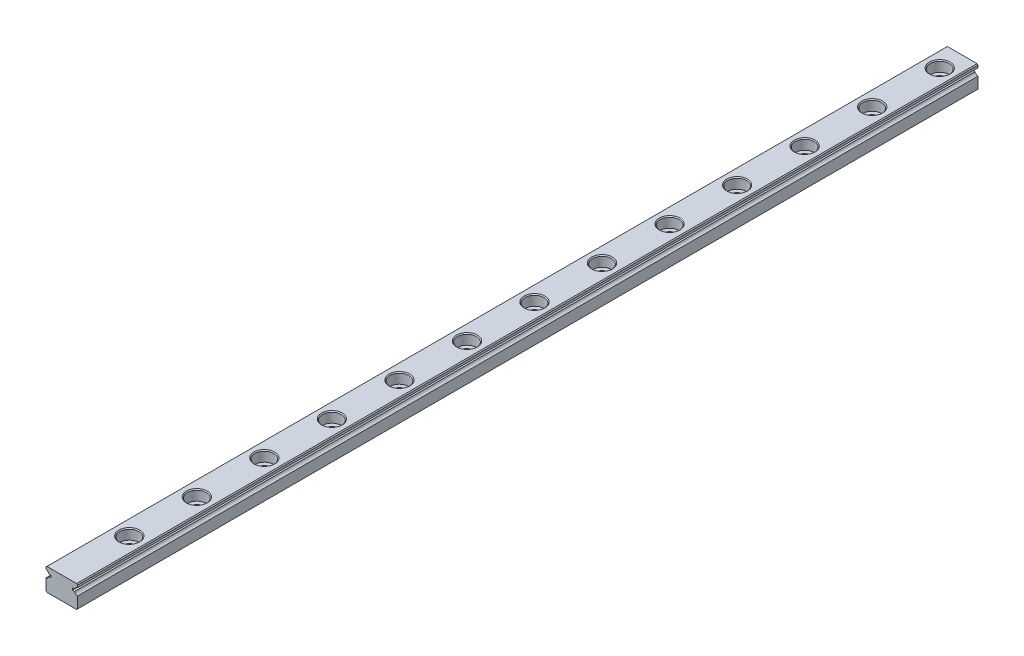
SolidWorks part; units mm, degrees
ref_plane "Спереди" through (0, 0, 0) normal (0, 0, 1) x (1, 0, 0)
ref_plane "Сверху" through (0, 0, 0) normal (0, 1, 0) x (1, 0, 0)
ref_plane "Справа" through (0, 0, 0) normal (1, 0, 0) x (0, 0, -1)
sketch "Sketch1" plane through (0, 0, 0) normal (0, 0, 1) x (1, 0, 0)
  line L0 (0, 0) -> (0, 4.3706) construction
  line L1 (-3.3, -2.5) -> (3.3, -2.5)
  line L2 (-3.5, -2.3) -> (-3.5, 0.2063)
  line L3 (-3.3, 2.5) -> (3.3, 2.5)
  line L4 (3.5, -2.3) -> (3.5, 0.2063)
  line L5 (-3.5, -2.5) -> (3.5, 2.5) construction
  line L6 (-3.5, 2.5) -> (3.5, -2.5) construction
  line L7 (-3.5, 1.7937) -> (-3.5, 2.3)
  line L8 (3.5, 1.7937) -> (3.5, 2.3)
  line L9 (-3.5, -2.3) -> (-3.3, -2.5)
  line L10 (3.3, -2.5) -> (3.5, -2.3)
  line L11 (3.3, 2.5) -> (3.5, 2.3)
  line L12 (-3.5, 2.3) -> (-3.3, 2.5)
  line L13 (2.8401, 0.75) -> (2.3401, 0.75)
  line L14 (-2.8401, 0.75) -> (-2.3401, 0.75)
  line L15 (2.3401, 0.75) -> (2.3401, 1.25)
  line L16 (-2.8401, 1.25) -> (-2.3401, 1.25)
  line L17 (-2.3401, 0.75) -> (-2.3401, 1.25)
  line L18 (2.8401, 1.25) -> (2.3401, 1.25)
  arc A0 (-3.5, 1.7937) -> (-2.8401, 1.25) centre (-3.6, 1) cw
  arc A1 (3.5, 1.7937) -> (2.8401, 1.25) centre (3.6, 1) ccw
  arc A2 (-2.8401, 0.75) -> (-3.5, 0.2063) centre (-3.6, 1) cw
  arc A3 (2.8401, 0.75) -> (3.5, 0.2063) centre (3.6, 1) ccw
  point P0 (0, 0)
  dimension "D4" = 0.8
  dimension "D5" = 0.1
  dimension "D1" = 7
  dimension "D2" = 5
  dimension "D3" = 1.5
  dimension "D6" = 0.5
  dimension "D7" = 0.5
extrude "Extrude1" add sketch "Sketch1" along normal blind 200
sketch "Sketch2" plane through (0, 2.5, 0) normal (0, 1, 0) x (1, 0, 0)
  line L0 (0, 0) -> (0, -5) construction
  circle A0 centre (0, -5) radius 1.2
  circle A1 centre (0, -5) radius 2.1
  dimension "D1" = 2.4
  dimension "D2" = 4.2
  dimension "D3" = 5
extrude "Extrude2" cut sketch "Sketch2" against normal up to next contours A0 region at (0, 2.5, 5)
extrude "Extrude4" cut sketch "Sketch" against normal blind 2.3
sketch "Sketch" plane through (0, 2.5, 0) normal (0, 1, 0) x (1, 0, 0) same geometry as "Sketch2"
chamfer "Chamfer1" distance 0.2 angle 45 2 edges at (0, -2.5, 6.2) (0, 2.5, 7.1)
pattern_linear "LPattern1" count 13 spacing 15 along (0, 0, 1) of "Extrude4", "Chamfer1", "Extrude2"
